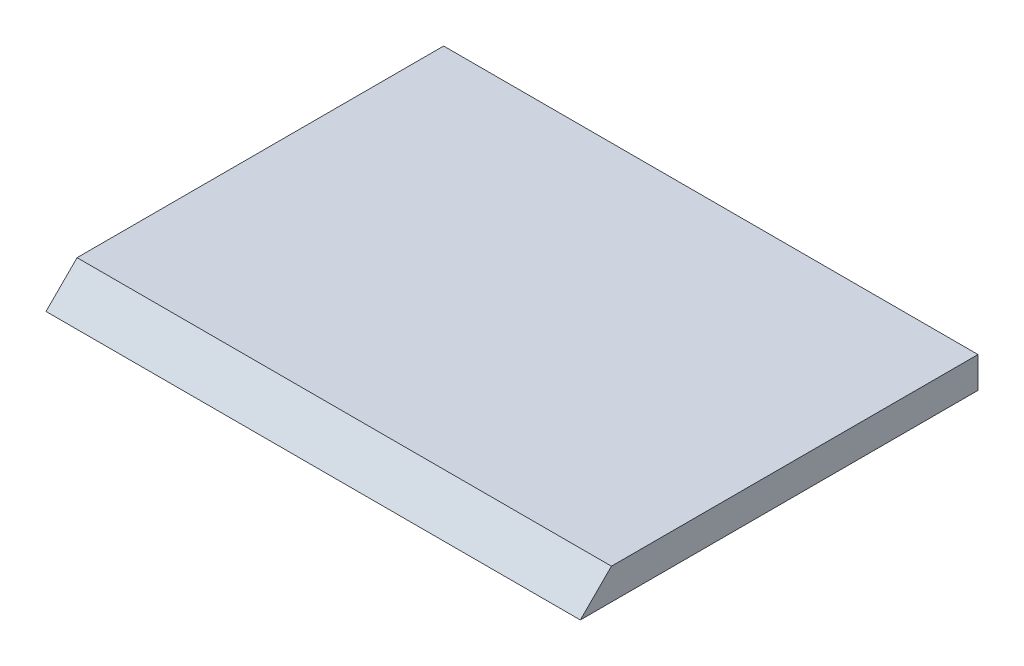
SolidWorks part; units mm, degrees
ref_plane "Front Plane" through (0, 0, 0) normal (0, 0, 1) x (1, 0, 0)
ref_plane "Top Plane" through (0, 0, 0) normal (0, 1, 0) x (1, 0, 0)
ref_plane "Right Plane" through (0, 0, 0) normal (1, 0, 0) x (0, 0, -1)
sketch "Sketch1" plane through (0, 0, 0) normal (0, 1, 0) x (1, 0, 0)
  line L8 (-5.461, 4.064) -> (5.461, 4.064)
  line L9 (-5.461, 4.064) -> (-5.461, -4.064)
  line L10 (-5.461, -4.064) -> (5.461, -4.064)
  line L11 (5.461, 4.064) -> (5.461, -4.064)
  line L12 (-5.461, 4.064) -> (5.461, -4.064) construction
  line L13 (-5.461, -4.064) -> (5.461, 4.064) construction
  point P5 (0, 0)
  dimension "D1" = 8.128
  dimension "D2" = 10.922
extrude "Boss-Extrude1" add sketch "Sketch1" along normal blind 0.635
chamfer "Chamfer1" distance 0.635 angle 45 1 edges at (0, 0.635, 4.064)
